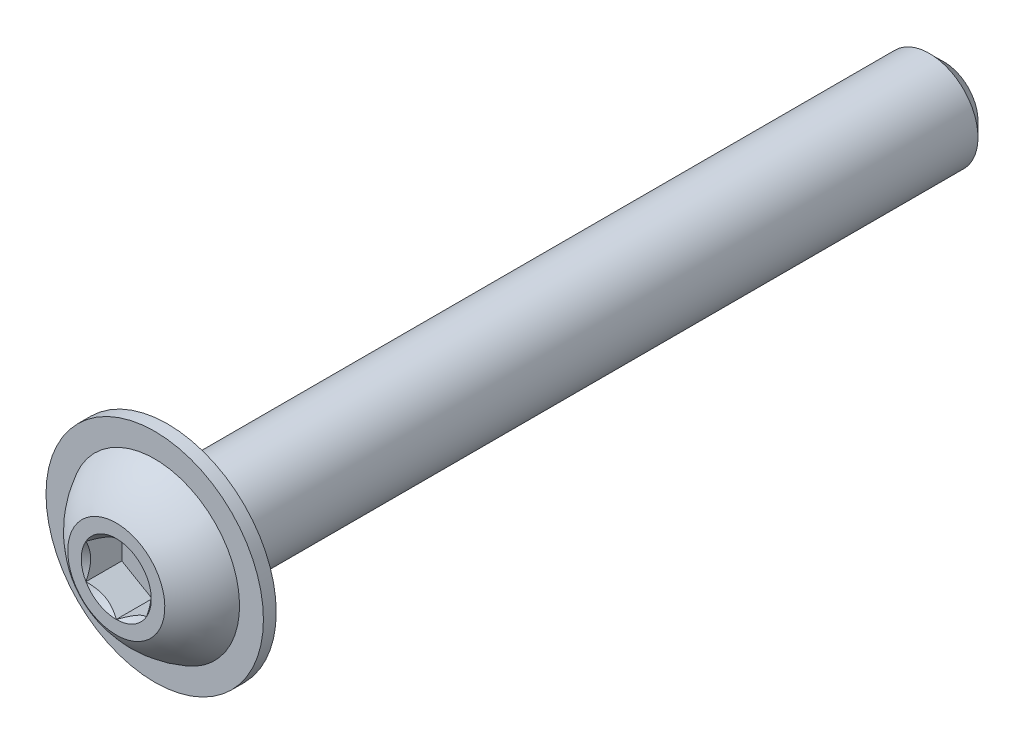
SolidWorks part; units mm, degrees
ref_plane "Front" through (0, 0, 0) normal (0, 0, 1) x (1, 0, 0)
ref_plane "Top" through (0, 0, 0) normal (0, 1, 0) x (1, 0, 0)
ref_plane "Right" through (0, 0, 0) normal (1, 0, 0) x (0, 0, -1)
sketch "Sketch1" plane through (0, 0, 0) normal (1, 0, 0) x (0, 0, -1)
  line L2 (3.3528, 3.175) -> (54.1528, 3.175)
  line L3 (54.1528, 3.175) -> (54.1528, 0)
  line L4 (54.1528, 0) -> (3.3528, 0)
  line L6 (2.5146, 5.5499) -> (3.3528, 5.5499) construction
  line L7 (54.1528, 3.175) -> (54.1528, -3.175) construction
  line L8 (0, 0) -> (3.3528, 0) construction
  line L9 (3.3528, 5.5499) -> (3.3528, -5.5499) construction
  line L11 (3.3528, 3.175) -> (3.3528, 0)
  line L13 (0, 1.9844) -> (0, -1.9844) construction
  line L14 (0, 1.9844) -> (0, 3.175) construction
  line L15 (2.5146, 5.5499) -> (2.5146, 7.112) construction
  line L16 (2.5146, 7.112) -> (3.3528, 7.112) construction
  line L17 (3.3528, 7.112) -> (3.3528, 5.5499) construction
  line L18 (3.3528, 7.112) -> (3.3528, -7.112) construction
  arc A3 (0, 3.175) -> (2.5146, 5.5499) centre (5.3774, 0) cw construction
  dimension "D1" = 0.8382
revolve "Revolve1" add sketch "Sketch1" angle 360 mid plane about L4
sketch "Sketch3" plane through (0, 0, -54.1528) normal (0, 0, -1) x (-1, 0, 0)
  circle A0 centre (0, 0) radius 3.175
curve "Helix/Spiral1" pitch 1.27 height 52.07 turns 41
sketch "Sketch2" plane through (0, 0, 0) normal (1, 0, 0) x (0, 0, -1)
  line L0 (54.1528, 3.175) -> (55.2641, 3.175)
  line L1 (55.2641, 3.175) -> (54.7878, 2.3501)
  line L2 (54.7878, 2.3501) -> (54.629, 2.3501)
  line L3 (54.629, 2.3501) -> (54.1528, 3.175)
  line L4 (54.3909, 2.7626) -> (55.0259, 2.7626) construction
  dimension "D1" = 60
  dimension "D2" = 0.1588
  dimension "D3" = 0.635
chamfer "Chamfer1" distance 0.9525 angle 45 1 edges at (0, 3.175, -54.1528)
sweep "Cut-Sweep1" [suppressed] cut profiles "Sketch2" path "Helix/Spiral1"
sketch "Sketch7" plane through (0, 0, 0) normal (1, 0, 0) x (0, 0, -1)
  line L6 (2.5146, 5.5499) -> (3.3528, 5.5499) construction
  line L8 (0, 0) -> (3.3528, 0) construction
  line L11 (3.3528, 5.5499) -> (3.3528, -5.5499) construction
  line L12 (2.5146, 5.5499) -> (3.3528, 5.5499)
  line L13 (0, 0) -> (3.3528, 0)
  line L14 (0, 1.9844) -> (0, -1.9844) construction
  line L15 (3.3528, 5.5499) -> (3.3528, 0)
  line L16 (0, 3.175) -> (0, 0)
  arc A2 (2.5146, 5.5499) -> (0, 3.175) centre (5.3774, 0) ccw construction
  arc A3 (2.5146, 5.5499) -> (0, 3.175) centre (5.3774, 0) ccw
revolve "Revolve2" add sketch "Sketch7" angle 360 mid plane about L13
sketch "Sketch11" plane through (0, 0, -3.3528) normal (0, 0, -1) x (-1, 0, 0)
  circle A0 centre (0, 0) radius 7.112
extrude "Boss-Extrude3" add sketch "Sketch11" against normal up to vertex (0.8382 mm away) up to point (0, 5.5499, -2.5146)
sketch "Sketch5" plane through (0, 0, 0) normal (0, 0, 1) x (1, 0, 0)
  line L1 (1.9844, -1.1457) -> (1.9844, 1.1457)
  line L2 (1.9844, 1.1457) -> (0, 2.2914)
  line L3 (0, 2.2914) -> (-1.9844, 1.1457)
  line L4 (-1.9844, 1.1457) -> (-1.9844, -1.1457)
  line L5 (-1.9844, -1.1457) -> (0, -2.2914)
  line L6 (0, -2.2914) -> (1.9844, -1.1457)
  circle A0 centre (0, 0) radius 1.9844 construction
extrude "Cut-Extrude2" cut sketch "Sketch5" against normal blind 2.347
sketch "Sketch6" plane through (0, 0, 0) normal (0, 0, 1) x (1, 0, 0)
  circle A0 centre (0, 0) radius 2.2914
extrude "Cut-Extrude3" cut sketch "Sketch6" against normal blind 2.347 draft 45
sketch "Sketch9" [suppressed] plane through (0, 0, -5.0546) normal (0, 0, 1) x (1, 0, 0)
  circle A2 centre (0, 0) radius 4.7625
extrude "Boss-Extrude2" [suppressed] add sketch "Sketch9" against normal offset from surface (6.35 mm away) 31.75
sketch "Sketch10" plane through (0, 0, 0) normal (1, 0, 0) x (0, 0, -1)
  line L0 (54.1528, 3.175) -> (54.1528, -3.175) construction
  point P0 (52.2478, -3.175)
  dimension "D1" = 1.905
equation "\"D3@Helix/Spiral1\" = \"Lg@Sketch1\" + \"D4@Helix/Spiral1\""
equation "\"D2@Sketch2\" = \"D4@Helix/Spiral1\" * .125"
equation "\"D3@Sketch2\" = \"D4@Helix/Spiral1\" * .5"
equation "\"D1@Chamfer1\" = \"D4@Helix/Spiral1\" * .75"
equation "\"D1@Cut-Extrude2\" = \"Head Ht@Sketch1\" * .7"
equation "\"D1@Sketch1\" = \"Head Ht@Sketch1\" * .25"
equation "\"D1@Sketch10\" = \"D4@Helix/Spiral1\" * 1.5"
equation "\"D1@Cut-Extrude3\" = \"D1@Cut-Extrude2\""
